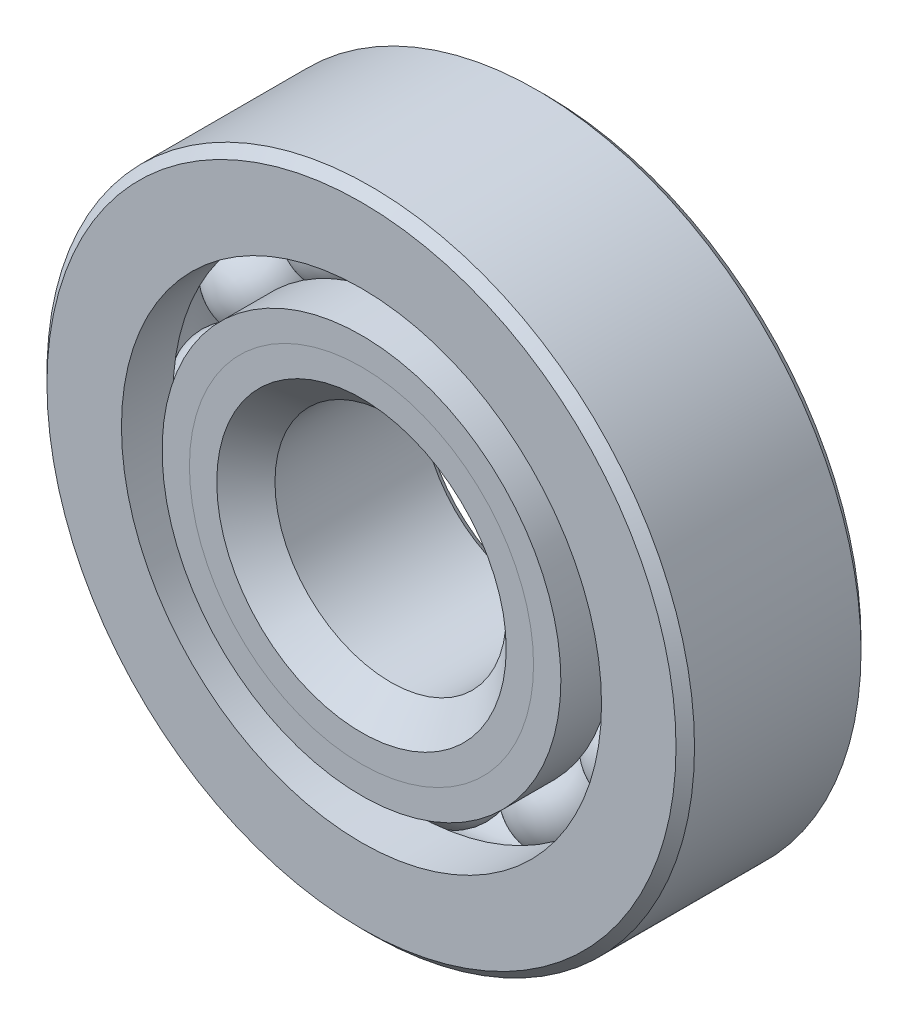
SolidWorks part; units mm, degrees
ref_plane "Front Plane" through (0, 0, 0) normal (0, 0, 1) x (1, 0, 0)
ref_plane "Top Plane" through (0, 0, 0) normal (0, 1, 0) x (1, 0, 0)
ref_plane "Right Plane" through (0, 0, 0) normal (1, 0, 0) x (0, 0, -1)
sketch "Sketch1" plane through (0, 0, 0) normal (1, 0, 0) x (0, 0, -1)
  line L0 (-3.175, 0) -> (3.175, 0) construction
  line L1 (0, 11.1125) -> (0, -11.1125) construction
  line L2 (2.8575, 11.1125) -> (-2.8575, 11.1125)
  line L3 (-2.8575, 11.1125) -> (-3.175, 10.795)
  line L4 (-3.175, 10.795) -> (-3.175, 8.2384)
  line L5 (-3.175, 8.2384) -> (-1.4111, 8.2384)
  line L6 (3.175, 8.2384) -> (1.4111, 8.2384)
  line L7 (3.175, 10.795) -> (3.175, 8.2384)
  line L8 (2.8575, 11.1125) -> (3.175, 10.795)
  line L9 (0, 11.1125) -> (0, 7.5406) construction
  line L10 (0, 7.5406) -> (0, 3.9688) construction
  arc A0 (-1.4111, 8.2384) -> (1.4111, 8.2384) centre (0, 7.5406) cw
  point P14 (0, 3.9688)
  dimension "D3" = 2.8222
  dimension "D1" = 45
  dimension "Width" = 6.35
  dimension "OD" = 22.225
  dimension "D2" = 0.3175
  dimension "Shaft Dia" = 7.9375
  dimension "D4" = 0.6978
revolve "Revolve1" add sketch "Sketch1" angle 360 about L0
sketch "Sketch2" plane through (0, 0, 0) normal (1, 0, 0) x (0, 0, -1)
  line L0 (-3.175, 6.8428) -> (-1.4111, 6.8428)
  line L1 (-3.175, 10.795) -> (-3.175, -10.795) construction
  line L2 (-3.175, 6.8428) -> (-3.175, 5.9052)
  line L3 (-3.175, 5.9052) -> (-2.2374, 4.9676)
  line L4 (-2.2374, 4.9676) -> (0, 4.9676)
  line L5 (0, 11.1125) -> (0, -11.1125) construction
  line L6 (0, 4.9676) -> (0, 5.9664)
  line L7 (0, 5.9664) -> (0, 3.9688) construction
  line L8 (-3.175, 6.8428) -> (-3.175, 4.9676) construction
  line L9 (-3.175, 4.9676) -> (-2.2374, 4.9676) construction
  arc A0 (-1.4111, 6.8428) -> (0, 5.9664) centre (0, 7.5406) ccw
  arc A1 (1.4111, 8.2384) -> (-1.4111, 8.2384) centre (0, 7.5406) ccw construction
  circle A2 centre (0, 7.5406) radius 1.5742 construction
  dimension "D1" = 45
revolve "Revolve2" add sketch "Sketch2" angle 360 about L0
sketch "Sketch3" plane through (0, 0, 0) normal (1, 0, 0) x (0, 0, -1)
  line L0 (-3.175, 5.9052) -> (-2.2374, 4.9676)
  line L1 (-2.2374, 4.9676) -> (0, 4.9676)
  line L2 (0, 4.9676) -> (0, 5.9664)
  line L3 (-3.175, 5.9052) -> (-3.175, 4.9676)
  line L4 (-3.175, 6.8428) -> (-3.175, 4.9676) construction
  line L5 (-3.175, 4.9676) -> (-2.1762, 3.9688)
  line L6 (-2.1762, 3.9688) -> (2.8575, 3.9688)
  line L7 (2.8575, 11.1125) -> (2.8575, -11.1125) construction
  line L8 (2.8575, 3.9688) -> (3.175, 4.2862)
  line L9 (3.175, -10.795) -> (3.175, 10.795) construction
  line L10 (3.175, 4.2862) -> (3.175, 6.8428)
  line L11 (3.175, 6.8428) -> (1.4111, 6.8428)
  line L13 (2.8575, 11.1125) -> (3.175, 10.795) construction
  circle A0 centre (0, 7.5406) radius 1.5742 construction
  arc A1 (1.4111, 6.8428) -> (0, 5.9664) centre (0, 7.5406) cw
revolve "Revolve3" add sketch "Sketch3" angle 360 about L0
sketch "Sketch4" plane through (0, 0, 0) normal (1, 0, 0) x (0, 0, -1)
  line L0 (-1.5742, 7.5406) -> (1.5742, 7.5406)
  circle A1 centre (0, 7.5406) radius 1.5742 construction
  arc A2 (-1.5742, 7.5406) -> (1.5742, 7.5406) centre (0, 7.5406) cw
  arc A3 (1.4111, 8.2384) -> (-1.4111, 8.2384) centre (0, 7.5406) ccw construction
revolve "Revolve4" add sketch "Sketch4" angle 360 about L0
ref_axis "Axis1" through (0, 0, -3.175) along (0, 0, 1)
pattern_circular "CirPattern1" count 12 every 30 about axis through (0, 0, -3.175) along (0, 0, 1) of bodies 104
equation "\"D2@Sketch1\" = \"Width@Sketch1\"*.05"
equation "\"D3@Sketch1\" = \"Width@Sketch1\"/2.25"
equation "\"D4@Sketch1\" = (((\"OD@Sketch1\"-\"Width@Sketch1\")/2)/3.25)/3.5"
equation "\"D2@CirPattern1\" = 360/\"Balls@CirPattern1\""
